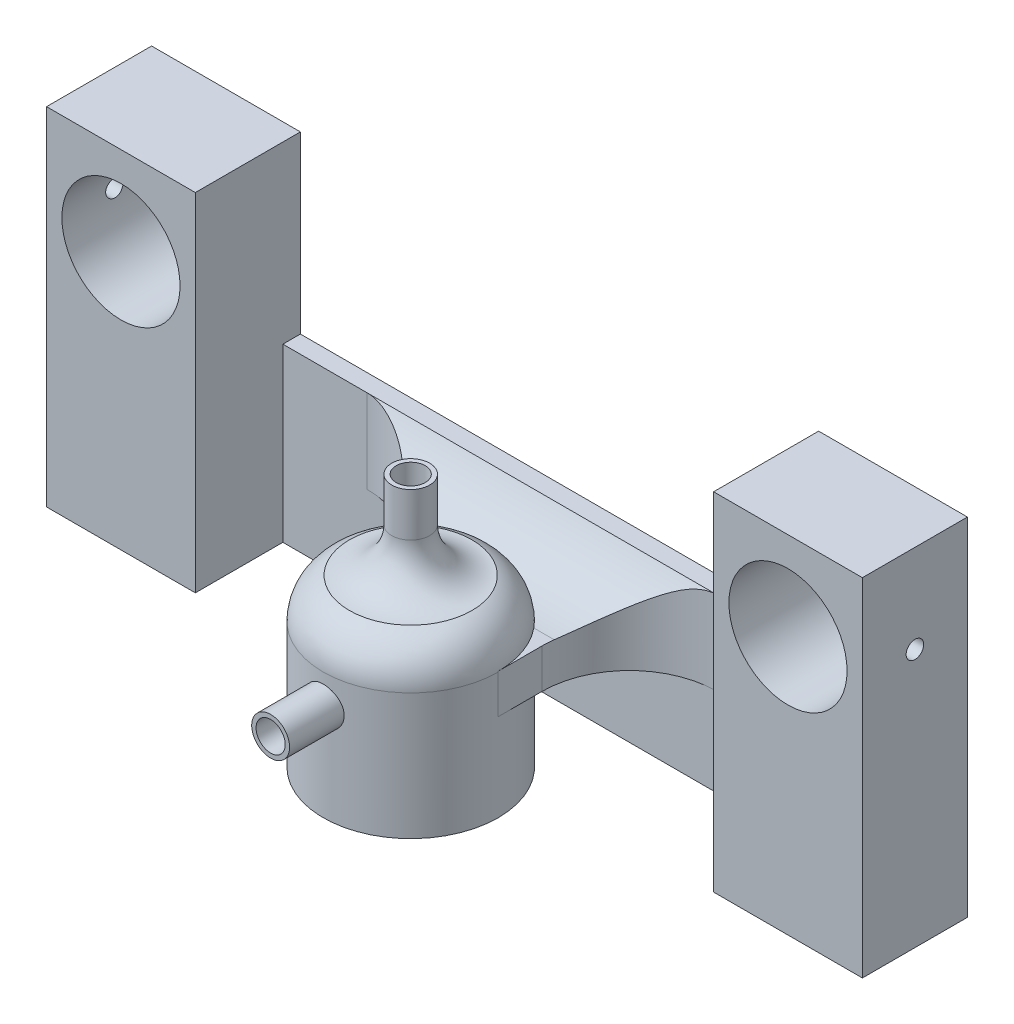
SolidWorks part; units mm, degrees
ref_plane "Front Plane" through (0, 0, 0) normal (0, 0, 1) x (1, 0, 0)
ref_plane "Top Plane" through (0, 0, 0) normal (0, 1, 0) x (1, 0, 0)
ref_plane "Right Plane" through (0, 0, 0) normal (1, 0, 0) x (0, 0, -1)
sketch "Sketch1" plane through (0, 0, 0) normal (0, 1, 0) x (1, 0, 0)
  circle A0 centre (0, 0) radius 6
  circle A1 centre (0, 0) radius 7
extrude "Boss-Extrude1" add sketch "Sketch1" along normal blind 15
sketch "Sketch2" plane through (0, 15, 0) normal (0, 1, 0) x (1, 0, 0)
  circle A0 centre (0, 0) radius 2.165
  circle A1 centre (0, 0) radius 7
extrude "Boss-Extrude2" add sketch "Sketch2" along normal blind 2
fillet "Fillet1" radius 5 1 edges at (0, 15, 6)
sketch "Sketch3" plane through (0, 17, 0) normal (0, 1, 0) x (1, 0, 0)
  circle A0 centre (0, 0) radius 1.665
  circle A1 centre (0, 0) radius 2.165
extrude "Boss-Extrude3" add sketch "Sketch3" against normal blind 2 and the other way blind 10
sketch "Sketch4" plane through (0, 0, 0) normal (0, -1, 0) x (1, 0, 0)
  circle A0 centre (0, 0) radius 9
  circle A1 centre (0, 0) radius 10
extrude "Boss-Extrude4" add sketch "Sketch4" against normal blind 16 and the other way blind 2 separate body
sketch "Sketch5" plane through (0, 16, 0) normal (0, 1, 0) x (1, 0, 0)
  circle A0 centre (0, 0) radius 10
  circle A1 centre (0, 0) radius 7
extrude "Boss-Extrude5" add sketch "Sketch5" along normal blind 1
fillet "Fillet3" radius 5 1 edges at (0, 16, -9)
fillet "Fillet5" radius 5 1 edges at (0, 17, 2.165)
fillet "Fillet6" radius 5 1 edges at (0, 17, 10)
sketch "Sketch7" plane through (0, 27, 0) normal (0, 1, 0) x (1, 0, 0)
  line L0 (0, -2.165) -> (0, 2.165) construction
  circle A0 centre (0, 0) radius 2.165 construction
ref_plane "Plane1" through (0, 0, 10) normal (0, 0, 1) x (1, 0, 0)
sketch "Sketch8" plane through (0, 0, 10) normal (0, 0, 1) x (1, 0, 0)
  circle A0 centre (0, 9.0607) radius 1.665
extrude "Cut-Extrude3" cut sketch "Sketch8" against normal blind 2
sketch "Sketch9" plane through (0, 0, 10) normal (0, 0, 1) x (1, 0, 0)
  circle A0 centre (0, 9.0607) radius 1.665
  circle A1 centre (0, 9.0607) radius 2.165
extrude "Boss-Extrude6" add sketch "Sketch9" along normal blind 6 and the other way blind 1
ref_plane "Plane2" through (0, 0, -10) normal (0, 0, -1) x (-1, 0, 0)
sketch "Sketch11" plane through (0, -2, 0) normal (0, -1, 0) x (1, 0, 0)
  line L5 (-10, 0) -> (-10, -15)
  line L6 (10, 0) -> (10, -15)
  line L7 (-10, -15) -> (10, -15)
  arc A0 (-10, 0) -> (10, 0) centre (0, 0) ccw
  circle A1 centre (0, 0) radius 10 construction
extrude "Boss-Extrude7" add sketch "Sketch11" against normal blind 14.5
sketch "Sketch12" plane through (0, -2, 0) normal (0, -1, 0) x (-1, 0, 0)
  line L0 (10, 0) -> (10, 15)
  line L1 (10, 15) -> (-10, 15)
  line L2 (-10, 15) -> (-10, 0)
  arc A0 (10, 0) -> (-10, 0) centre (0, 0) ccw
extrude "Cut-Extrude4" cut sketch "Sketch12" against normal blind 10
sketch "Sketch13" plane through (0, 0, -15) normal (0, 0, -1) x (-1, 0, 0)
  line L1 (-46.6, -2.0538) -> (46.6, -2.0538)
  line L2 (-46.6, -2.0538) -> (-46.6, 17.5538)
  line L3 (-46.6, 17.5538) -> (46.6, 17.5538)
  line L4 (46.6, -2.0538) -> (46.6, 17.5538)
  line L5 (-46.6, -2.0538) -> (46.6, 17.5538) construction
  line L6 (-46.6, 17.5538) -> (46.6, -2.0538) construction
  point P0 (0, 7.75)
extrude "Boss-Extrude8" add sketch "Sketch13" along normal blind 2
fillet "Fillet8" radius 10 2 edges at (10, 10.25, -15) (-10, 10.25, -15)
fillet "Fillet9" radius 10 1 edges at (0, 12.5, -15)
ref_plane "Plane3" through (0, 0, 0) normal (1, 0, 0) x (0, 0, -1)
sketch "Sketch20" plane through (0, 0, -15) normal (0, 0, 1) x (1, 0, 0)
  line L1 (46.6, 17.5538) -> (29.6043, 17.5538)
  line L2 (46.6, 17.5538) -> (46.6, 37.5538)
  line L3 (46.6, 37.5538) -> (29.6043, 37.5538)
  line L4 (29.6043, 17.5538) -> (29.6043, 37.5538)
extrude "Boss-Extrude10" add sketch "Sketch20" against normal blind 2 and the other way blind 10
sketch "Sketch23" plane through (0, 0, -17) normal (0, 0, -1) x (-1, 0, 0)
  line L0 (0, 27.4509) -> (-38.1, 27.4509) construction
  line L1 (0, 5.5) -> (0, -5.5) construction
sketch "Sketch24" plane through (0, 0, -17) normal (0, 0, -1) x (-1, 0, 0)
  circle A0 centre (-38.1, 27.4509) radius 6.75
extrude "Cut-Extrude10" cut sketch "Sketch24" against normal through all contours A0
sketch "Sketch26" plane through (0, 0, -5) normal (0, 0, 1) x (1, 0, 0)
  line L0 (44.85, 27.4509) -> (46.6, 27.4509) construction
  line L1 (46.6, 17.5538) -> (46.6, 37.5538) construction
  circle A0 centre (38.1, 27.4509) radius 6.75 construction
sketch "Sketch27" plane through (46.6, 0, 0) normal (1, 0, 0) x (0, 0, -1)
  line L0 (5, 27.4509) -> (17, 27.4509) construction
  line L1 (17, 37.5538) -> (17, -2.0538) construction
  circle A0 centre (11, 27.4509) radius 1
extrude "Cut-Extrude11" cut sketch "Sketch27" against normal up to next
mirror "Mirror10" about plane through (0, 0, 0) normal (1, 0, 0) of bodies 125
sketch "Sketch28" plane through (0, 0, -15) normal (0, 0, 1) x (1, 0, 0)
  line L1 (29.6043, 17.5538) -> (46.6, 17.5538)
  line L2 (29.6043, 17.5538) -> (29.6043, -2.0538)
  line L3 (29.6043, -2.0538) -> (46.6, -2.0538)
  line L4 (46.6, 17.5538) -> (46.6, -2.0538)
extrude "Boss-Extrude12" add sketch "Sketch28" along normal up to vertex (10 mm away) up to point (29.6043, 17.5538, -5)
sketch "Sketch29" plane through (0, 0, -15) normal (0, 0, 1) x (1, 0, 0)
  line L0 (29.6043, -2.0538) -> (-46.6, -2.0538) construction
  line L1 (-46.6, 17.5538) -> (-29.6043, 17.5538)
  line L2 (-46.6, 17.5538) -> (-46.6, -2.0538)
  line L3 (-46.6, -2.0538) -> (-29.6043, -2.0538)
  line L4 (-29.6043, 17.5538) -> (-29.6043, -2.0538)
extrude "Boss-Extrude13" add sketch "Sketch29" along normal up to surface (10 mm away) up to face at (-44.85, 27.4509, -5)
